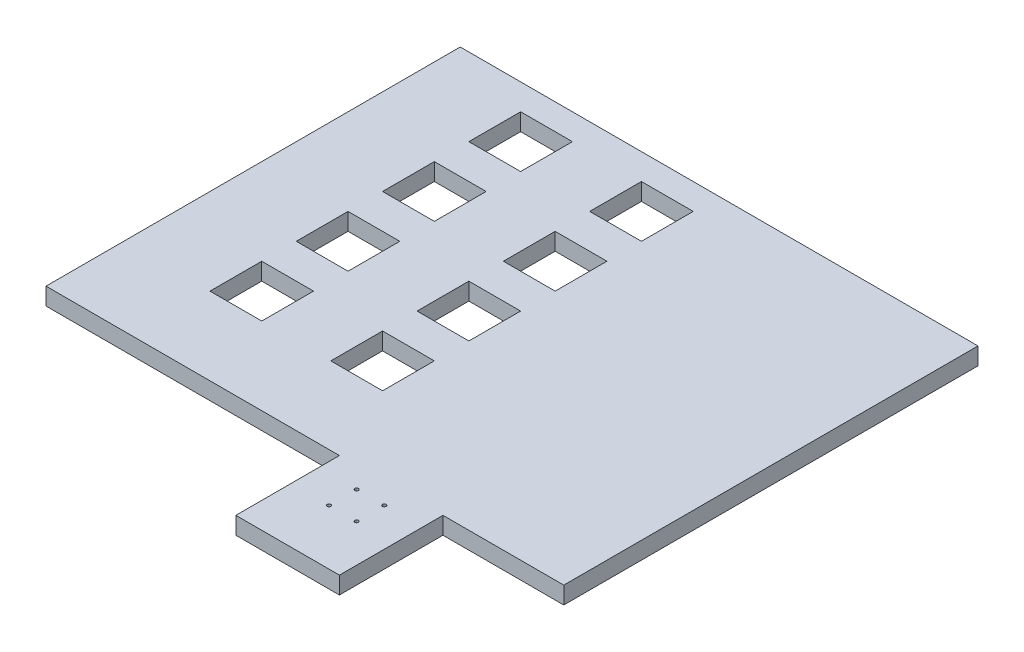
SolidWorks part; units mm, degrees
ref_plane "前基準面" through (0, 0, 0) normal (0, 0, 1) x (1, 0, 0)
ref_plane "上基準面" through (0, 0, 0) normal (0, 1, 0) x (1, 0, 0)
ref_plane "右基準面" through (0, 0, 0) normal (1, 0, 0) x (0, 0, -1)
sketch "草圖1" plane through (0, 0, 0) normal (0, 1, 0) x (1, 0, 0)
  line L0 (50, -1010.2) -> (50, 48989.8) construction
  line L1 (-150, -120) -> (20, -120)
  line L2 (-150, -120) -> (-150, 120)
  line L3 (-150, 120) -> (150, 120)
  line L4 (150, -120) -> (150, 120)
  line L5 (-150, -120) -> (150, 120) construction
  line L6 (-150, 120) -> (150, -120) construction
  line L7 (20, -120) -> (20, -180)
  line L8 (20, -180) -> (80, -180)
  line L9 (80, -180) -> (80, -120)
  line L10 (80, -120) -> (150, -120)
  point P0 (0, 0)
  point P10 (50, -180)
  dimension "D1" = 300
  dimension "D2" = 240
  dimension "D3" = 200
  dimension "D4" = 60
  dimension "D5" = 60
extrude "填料-伸長1" add sketch "草圖1" along normal blind 10
sketch "草圖2" plane through (0, 0, 0) normal (0, -1, 0) x (1, 0, 0)
  line L0 (-980, 140) -> (49020, 140) construction
  line L2 (50, -820) -> (50, 49180) construction
  line L3 (20, 180) -> (80, 180) construction
  line L4 (-150, 120) -> (20, 120) construction
  line L6 (60, 150) -> (40, 150)
  line L7 (60, 150) -> (60, 130)
  line L8 (60, 130) -> (40, 130)
  line L9 (40, 150) -> (40, 130)
  line L10 (60, 150) -> (40, 130) construction
  line L11 (60, 130) -> (40, 150) construction
  circle A0 centre (42, 132) radius 1.05
  circle A1 centre (42, 148) radius 1.05
  circle A2 centre (58, 132) radius 1.05
  circle A3 centre (58, 148) radius 1.05
  point P7 (50, 180)
  point P17 (50, 140)
  dimension "D4" = 2.1
  dimension "D1" = 20
  dimension "D2" = 8
  dimension "D3" = 8
  dimension "D5" = 20
  dimension "D6" = 20
extrude "除料-伸長1" cut sketch "草圖2" against normal blind 8 contours L6 L9 L8 L7 A3 A1 A0 A2 region at (50, 0, 140)
extrude "除料-伸長2" cut sketch "草圖2<3>" against normal through all contours A2 | A0 | A1 | A3
sketch "草圖2<3>" plane through (0, 0, 0) normal (0, -1, 0) x (1, 0, 0) same geometry as "草圖2"
sketch "草圖3" plane through (0, 10, 0) normal (0, 1, 0) x (1, 0, 0)
  line L0 (50, -1180) -> (50, 48820) construction
  line L1 (20, -180) -> (80, -180) construction
  line L2 (-50, -1006.6936) -> (-50, 48993.3064) construction
  line L3 (-150, 120) -> (-150, -120) construction
  line L5 (-150, -120) -> (20, -120) construction
  line L6 (-100, -75) -> (-70, -75)
  line L7 (-100, -75) -> (-100, -45)
  line L8 (-100, -45) -> (-70, -45)
  line L9 (-70, -75) -> (-70, -45)
  line L10 (-100, -75) -> (-70, -45) construction
  line L11 (-100, -45) -> (-70, -75) construction
  line L12 (-100, 5) -> (-70, 5)
  line L13 (-100, 5) -> (-100, -25)
  line L14 (-100, -25) -> (-70, -25)
  line L15 (-70, 5) -> (-70, -25)
  line L16 (-100, 5) -> (-70, -25) construction
  line L17 (-100, -25) -> (-70, 5) construction
  line L18 (-100, 55) -> (-70, 55)
  line L19 (-100, 55) -> (-100, 25)
  line L20 (-100, 25) -> (-70, 25)
  line L21 (-70, 55) -> (-70, 25)
  line L22 (-100, 55) -> (-70, 25) construction
  line L23 (-100, 25) -> (-70, 55) construction
  line L24 (-100, 105) -> (-70, 105)
  line L25 (-100, 105) -> (-100, 75)
  line L26 (-100, 75) -> (-70, 75)
  line L27 (-70, 105) -> (-70, 75)
  line L28 (-100, 105) -> (-70, 75) construction
  line L29 (-100, 75) -> (-70, 105) construction
  line L30 (0, -75) -> (-30, -75)
  line L31 (0, -75) -> (0, -45)
  line L32 (-30, -75) -> (-30, -45)
  line L33 (0, -45) -> (-30, -45)
  line L34 (0, -25) -> (-30, -25)
  line L35 (0, 5) -> (0, -25)
  line L36 (-30, 5) -> (-30, -25)
  line L37 (0, 5) -> (-30, 5)
  line L38 (0, 25) -> (-30, 25)
  line L39 (-30, 55) -> (-30, 25)
  line L40 (0, 55) -> (0, 25)
  line L41 (0, 55) -> (-30, 55)
  line L42 (0, 75) -> (-30, 75)
  line L43 (-30, 105) -> (-30, 75)
  line L44 (0, 105) -> (0, 75)
  line L45 (0, 105) -> (-30, 105)
  point P5 (50, -180)
  point P9 (-85, -60)
  point P14 (-85, -10)
  point P19 (-85, 40)
  point P24 (-85, 90)
  dimension "D1" = 100
  dimension "D2" = 30
  dimension "D3" = 30
  dimension "D4" = 30
  dimension "D5" = 30
  dimension "D6" = 20
  dimension "D7" = 20
  dimension "D8" = 20
  dimension "D9" = 45
  dimension "D10" = 20
extrude "除料-伸長3" cut sketch "草圖3" against normal through all
